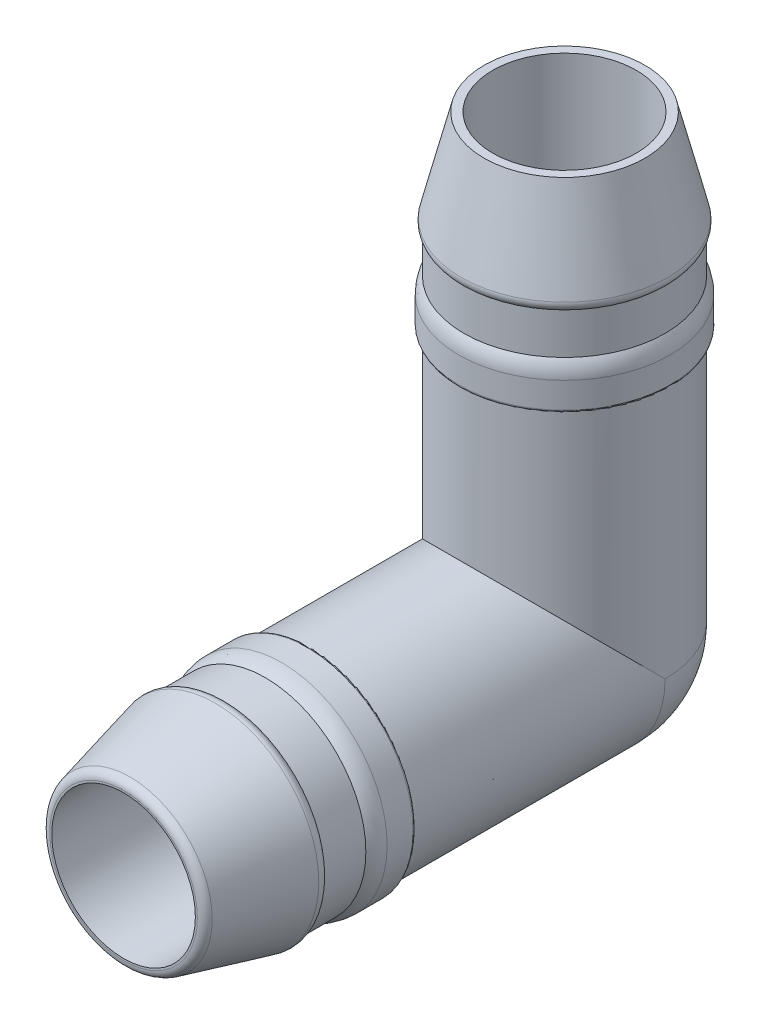
SolidWorks part; units mm, degrees
ref_plane "Front Plane" through (0, 0, 0) normal (0, 0, 1) x (1, 0, 0)
ref_plane "Top Plane" through (0, 0, 0) normal (0, 1, 0) x (1, 0, 0)
ref_plane "Right Plane" through (0, 0, 0) normal (1, 0, 0) x (0, 0, -1)
sketch "Sketch1" plane through (0, 0, 0) normal (0, 0, 1) x (1, 0, 0)
  circle A0 centre (0, 0) radius 3.5
  dimension "D1" = 7
extrude "Boss-Extrude1" add sketch "Sketch1" along normal blind 8.85
sketch "Sketch2" plane through (0, 0, 8.85) normal (0, 0, 1) x (1, 0, 0)
  circle A0 centre (0, 0) radius 3.675
  dimension "D1" = 7.35
extrude "Boss-Extrude2" add sketch "Sketch2" along normal blind 2
fillet "Fillet1" radius 1 1 edges at (3.675, 0, 10.85)
sketch "Sketch4" plane through (0, 0, 10.85) normal (0, 0, 1) x (1, 0, 0)
  circle A2 centre (0, 0) radius 3.5
  dimension "D1" = 7
extrude "Boss-Extrude3" add sketch "Sketch4" along normal blind 1 and the other way up to surface other way up to face at (3.675, 0, 9.85)
sketch "Sketch5" plane through (0, 0, 11.85) normal (0, 0, 1) x (1, 0, 0)
  circle A0 centre (0, 0) radius 3.675 construction
  circle A1 centre (0, 0) radius 3.675
extrude "Boss-Extrude4" add sketch "Sketch5" along normal blind 3.5 draft 14
fillet "Fillet2" radius 0.3 2 edges at (3.675, 0, 11.85) (2.8024, 0, 15.35)
fillet "Fillet3" radius 0.1 1 edges at (3.675, 0, 8.85)
sketch "Sketch7" plane through (0, 0, 0) normal (0, 1, 0) x (1, 0, 0)
  circle A0 centre (0, 0) radius 3.5
  dimension "D1" = 7
extrude "Boss-Extrude5" add sketch "Sketch7" along normal blind 8.85
sketch "Sketch8" plane through (0, 8.85, 0) normal (0, 1, 0) x (1, 0, 0)
  circle A0 centre (0, 0) radius 3.675
  dimension "D1" = 7.35
extrude "Boss-Extrude6" add sketch "Sketch8" along normal blind 2
fillet "Fillet4" radius 1 1 edges at (0, 10.85, 3.675)
sketch "Sketch9" plane through (0, 10.85, 0) normal (0, 1, 0) x (1, 0, 0)
  circle A2 centre (0, 0) radius 3.5
  dimension "D1" = 7
extrude "Boss-Extrude7" add sketch "Sketch9" along normal blind 1 and the other way up to surface other way up to face at (0, 9.85, 3.675)
sketch "Sketch10" plane through (0, 11.85, 0) normal (0, 1, 0) x (1, 0, 0)
  circle A0 centre (0, 0) radius 3.675 construction
  circle A1 centre (0, 0) radius 3.675
extrude "Boss-Extrude8" add sketch "Sketch10" along normal blind 3.5 draft 14
sketch "Sketch12" plane through (0, 0, 0) normal (1, 0, 0) x (0, 0, -1)
  line L3 (-3.35, 8.6657) -> (-3.35, -10.8948) construction
  line L4 (-4.8826, 3.35) -> (11.7144, 3.35) construction
sketch "Sketch13" plane through (0, 0, 15.35) normal (0, 0, 1) x (1, 0, 0)
  circle A0 centre (0, 0) radius 2.5
  dimension "D1" = 5
ref_plane "Plane1" through (0, 0, 3.5) normal (0, 0, 1) x (1, 0, 0)
sketch "Sketch14" plane through (0, 15.35, 0) normal (0, 1, 0) x (1, 0, 0)
  circle A0 centre (0, 0) radius 2.5
  dimension "D1" = 5
sketch "Sketch15" plane through (0, 0, 0) normal (0, 0, -1) x (-1, 0, 0)
  line L0 (-3.5, 0) -> (3.5, 0)
  arc A3 (-3.5, 0) -> (3.5, 0) centre (0, 0) ccw
  dimension "D1" = 7
sketch "Sketch18" plane through (0, 0, 0) normal (0, 1, 0) x (1, 0, 0)
  line L0 (-3.7726, 0) -> (49996.2274, 0) construction
revolve "Revolve1" add sketch "Sketch15" angle 90 about L0 reverse direction yes
sketch "Sketch11" plane through (0, 15.35, 0) normal (0, 1, 0) x (1, 0, 0)
  circle A0 centre (0, 0) radius 2.5
  dimension "D1" = 5
fillet "Fillet5" radius 0.3 1 edges at (0, 11.85, 3.675)
fillet "Fillet6" radius 0.1 1 edges at (0, 8.85, 3.675)
ref_plane "Plane2" through (0, 3.5, 0) normal (0, 1, 0) x (1, 0, 0)
sketch "Sketch19" plane through (0, 0, 0) normal (1, 0, 0) x (0, 0, -1)
  line L0 (-15.35, 0) -> (-3.5, 0)
  line L1 (-15.35, 2.5) -> (-15.35, -2.5) construction
  line L2 (-3.5, 4.0425) -> (-3.5, -4.0425) construction
  line L4 (0, 3.5) -> (0, 16.1747)
  line L5 (4.0425, 3.5) -> (-4.0425, 3.5) construction
  line L6 (0, 4.0425) -> (0, -4.0425) construction
  arc A0 (-3.5, 0) -> (0, 3.5) centre (-3.5, 3.5) ccw
  point P7 (-3.5, 0)
  point P15 (0, 0)
sweep "Cut-Sweep2" cut profiles "Sketch13" path "Sketch19"
